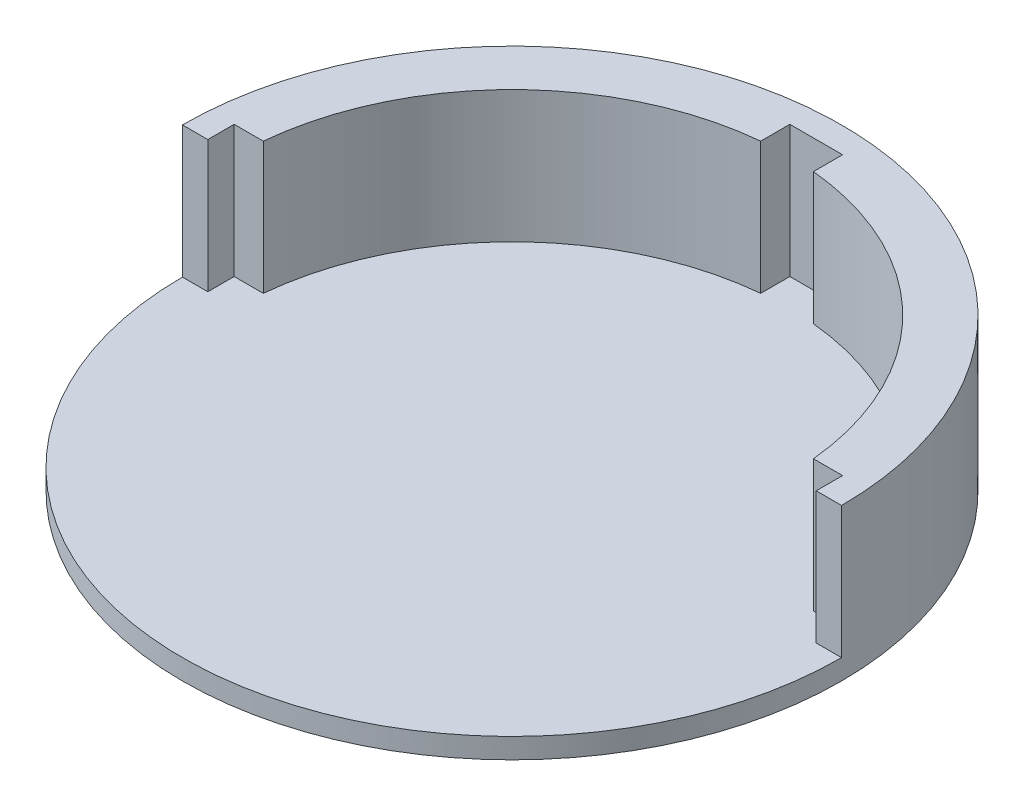
SolidWorks part; units mm, degrees
ref_plane "Front Plane" through (0, 0, 0) normal (0, 0, 1) x (1, 0, 0)
ref_plane "Top Plane" through (0, 0, 0) normal (0, 1, 0) x (1, 0, 0)
ref_plane "Right Plane" through (0, 0, 0) normal (1, 0, 0) x (0, 0, -1)
sketch "Sketch1" plane through (0, 0, 0) normal (0, 1, 0) x (1, 0, 0)
  circle A0 centre (0, 0) radius 32.5
  dimension "D1" = 65
extrude "Boss-Extrude1" add sketch "Sketch1" along normal blind 2
sketch "Sketch2" plane through (0, 2, 0) normal (0, 1, 0) x (1, 0, 0)
  line L0 (0, -55) -> (0, 55) construction
  line L1 (2.6, -30) -> (-2.6, -30)
  line L2 (2.6, -30) -> (2.6, -26.0456)
  line L3 (2.6, -26.0456) -> (-2.6, -26.0456)
  line L4 (-2.6, -30) -> (-2.6, -26.0456)
  line L5 (2.6, -30) -> (-2.6, -26.0456) construction
  line L6 (2.6, -26.0456) -> (-2.6, -30) construction
  line L7 (-30, -2.6) -> (-30, 2.6)
  line L8 (-30, -2.6) -> (-26.0456, -2.6)
  line L9 (-30, 2.6) -> (-26.0456, 2.6)
  line L10 (-26.0456, -2.6) -> (-26.0456, 2.6)
  line L11 (-2.6, 30) -> (2.6, 30)
  line L12 (-2.6, 30) -> (-2.6, 26.0456)
  line L13 (2.6, 30) -> (2.6, 26.0456)
  line L14 (-2.6, 26.0456) -> (2.6, 26.0456)
  line L15 (30, 2.6) -> (30, -2.6)
  line L16 (30, 2.6) -> (26.0456, 2.6)
  line L17 (30, -2.6) -> (26.0456, -2.6)
  line L18 (26.0456, 2.6) -> (26.0456, -2.6)
  circle A0 centre (0, 0) radius 27.1
  circle A1 centre (0, 0) radius 27.25
  circle A2 centre (0, 0) radius 32.5
  point P4 (0, -28.0228)
  circle M7 centre (0, 0) radius 32.5
  dimension "D1" = 54.5
  dimension "D2" = 54.2
  dimension "D3" = 30
  dimension "D4" = 5.2
  dimension "D5" = 4
extrude "Boss-Extrude2" add sketch "Sketch2" along normal blind 13 contours A0 L2 L1 L4 L8 L7 L9 L12 L11 L13 L16 L15 L17 M7 region at (-31.5808, 2, 0)
sketch "Sketch3" plane through (0, 0, 0) normal (0, -1, 0) x (1, 0, 0)
  circle A5 centre (0, 0) radius 5
  dimension "D1" = 10
extrude "Cut-Extrude2" [suppressed] cut sketch "Sketch3" against normal up to next contours A5
sketch "Sketch5" plane through (0, 0, 0) normal (0, -1, 0) x (1, 0, 0)
  line L1 (-9, -5.5) -> (9, -5.5) construction
  line L2 (-9, -5.5) -> (-9, 5.5) construction
  line L3 (-9, 5.5) -> (9, 5.5) construction
  line L4 (9, -5.5) -> (9, 5.5) construction
  line L5 (-9, -5.5) -> (9, 5.5) construction
  line L6 (-9, 5.5) -> (9, -5.5) construction
  circle A0 centre (9, 5.5) radius 1.3
  circle A1 centre (9, -5.5) radius 1.3
  circle A2 centre (-9, -5.5) radius 1.3
  circle A3 centre (-9, 5.5) radius 1.3
  point P0 (0, 0)
  dimension "D1" = 2.6
  dimension "D2" = 18
  dimension "D3" = 11
extrude "Cut-Extrude3" [suppressed] cut sketch "Sketch5" against normal up to next
sketch "Sketch6" plane through (0, 15, 0) normal (0, 1, 0) x (1, 0, 0)
  line L0 (-8.25, 0) -> (8.25, 0) construction
  line L1 (35.8547, 0) -> (-35.5353, 0)
  line L2 (35.8547, 0) -> (35.8547, -35.7749)
  line L3 (35.8547, -35.7749) -> (-35.5353, -35.7749)
  line L4 (-35.5353, 0) -> (-35.5353, -35.7749)
extrude "Cut-Extrude4" cut sketch "Sketch6" against normal up to surface (13 mm away) up to face at (0, 2, 0)
sketch "Sketch7" [suppressed] plane through (0, 0, 0) normal (1, 0, 0) x (0, 0, -1)
  line L0 (0, 8.25) -> (0, -8.25) construction
  line L1 (0, 2) -> (12, 2)
  line L2 (0, 2) -> (0, 5)
  line L3 (0, 5) -> (12, 5)
  line L4 (12, 2) -> (12, 5)
  line L5 (0, 2) -> (-32.5, 2) construction
  dimension "D1" = 3
  dimension "D2" = 12
sketch "Sketch8" plane through (0, 0, 0) normal (0, 0, 1) x (1, 0, 0)
  line L1 (36, 17) -> (32.5, 17)
  line L3 (36, 5) -> (30.5, 5)
  line L4 (30.5, 15) -> (30.5, 5)
  line L5 (32.5, 15) -> (32.5, 2) construction
  line L6 (32.5, 15) -> (-32.5, 15) construction
  line L7 (32.5, 15) -> (30.5, 15)
  line L8 (32.5, 15) -> (32.5, 17)
  arc A0 (36, 5) -> (36, 17) centre (36, 11) ccw
  circle A1 centre (36, 11) radius 1.6
  dimension "D5" = 3.2
  dimension "D1" = 2
  dimension "D2" = 3.5
  dimension "D3" = 12
  dimension "D4" = 4
extrude "Boss-Extrude3" [suppressed] add sketch "Sketch8" against normal blind 2.5
mirror "Mirror1" [suppressed] about plane through (0, 0, 0) normal (1, 0, 0)
sketch3d "3DSketch1"
  line L0 (30, 2, 0) -> (30, 15, 0) construction
  point P0 (30, 8.317, 0)
other "Snap Hook1" [suppressed] parameters "BaseDepth"=2, "TopDepth"=2, "Width"=4, "HookHeight"=6, "Overhang"=2, "BodyHeight"=10, "Draft"=3, "LipHeight"=0
